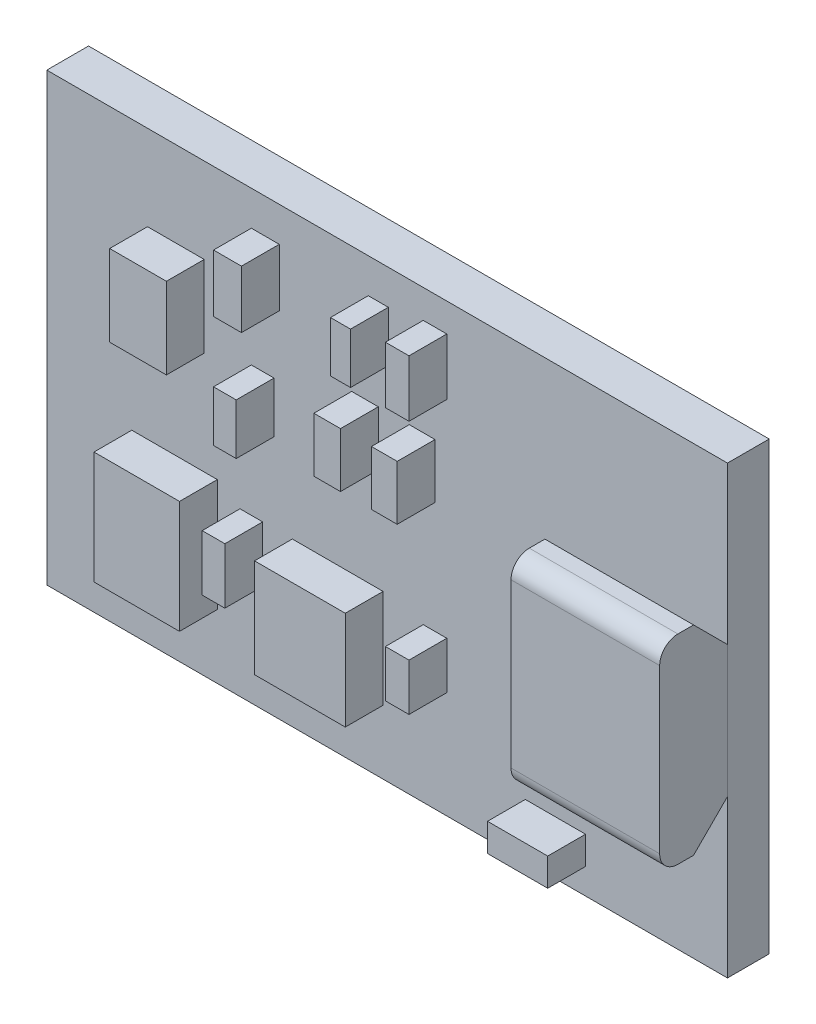
SolidWorks part; units mm, degrees
ref_plane "Спереди" through (0, 0, 0) normal (0, 0, 1) x (1, 0, 0)
ref_plane "Сверху" through (0, 0, 0) normal (0, 1, 0) x (1, 0, 0)
ref_plane "Справа" through (0, 0, 0) normal (1, 0, 0) x (0, 0, -1)
sketch "Эскиз1" plane through (0, 0, 0) normal (0, 0, 1) x (1, 0, 0)
  line L1 (-363.8203, 78.5154) -> (-337.7203, 78.5154)
  line L2 (-363.8203, 78.5154) -> (-363.8203, 61.4154)
  line L3 (-363.8203, 61.4154) -> (-337.7203, 61.4154)
  line L4 (-337.7203, 78.5154) -> (-337.7203, 61.4154)
  dimension "D1" = 17.1
  dimension "D2" = 26.1
extrude "Бобышка-Вытянуть1" add sketch "Эскиз1" along normal blind 1.6
sketch "Эскиз2" plane through (0, 0, 0) normal (0, 0, -1) x (-1, 0, 0)
  line L0 (337.7203, 61.4154) -> (337.7203, 78.5154) construction
  line L1 (350.9253, 67.6511) -> (354.4049, 67.6511)
  line L2 (350.9253, 67.6511) -> (350.9253, 63.8703)
  line L3 (350.9253, 63.8703) -> (354.4049, 63.8703)
  line L4 (354.4049, 67.6511) -> (354.4049, 63.8703)
  line L5 (357.2823, 68.1864) -> (360.5612, 68.1864)
  line L6 (357.2823, 68.1864) -> (357.2823, 63.8703)
  line L7 (357.2823, 63.8703) -> (360.5612, 63.8703)
  line L8 (360.5612, 68.1864) -> (360.5612, 63.8703)
  line L9 (357.7842, 75.2461) -> (359.959, 75.2461)
  line L10 (357.7842, 75.2461) -> (357.7842, 72.1345)
  line L11 (357.7842, 72.1345) -> (359.959, 72.1345)
  line L12 (359.959, 75.2461) -> (359.959, 72.1345)
  line L13 (348.4828, 67.3165) -> (349.3862, 67.3165)
  line L14 (348.4828, 67.3165) -> (348.4828, 65.5098)
  line L15 (348.4828, 65.5098) -> (349.3862, 65.5098)
  line L16 (349.3862, 67.3165) -> (349.3862, 65.5098)
  line L17 (343.163, 63.4688) -> (345.4716, 63.4688)
  line L18 (343.163, 63.4688) -> (343.163, 62.3982)
  line L19 (343.163, 62.3982) -> (345.4716, 62.3982)
  line L20 (345.4716, 63.4688) -> (345.4716, 62.3982)
  line L21 (348.4828, 77.4209) -> (349.3862, 77.4209)
  line L22 (348.4828, 77.4209) -> (348.4828, 75.2461)
  line L23 (348.4828, 75.2461) -> (349.3862, 75.2461)
  line L24 (349.3862, 77.4209) -> (349.3862, 75.2461)
  line L25 (350.7245, 77.1867) -> (351.4941, 77.1867)
  line L26 (350.7245, 77.1867) -> (350.7245, 75.2461)
  line L27 (350.7245, 75.2461) -> (351.4941, 75.2461)
  line L28 (351.4941, 77.1867) -> (351.4941, 75.2461)
  line L29 (348.9345, 73.6903) -> (349.9215, 73.6903)
  line L30 (348.9345, 73.6903) -> (348.9345, 71.5992)
  line L31 (348.9345, 71.5992) -> (349.9215, 71.5992)
  line L32 (349.9215, 73.6903) -> (349.9215, 71.5992)
  line L33 (351.1093, 73.6903) -> (352.1298, 73.6903)
  line L34 (351.1093, 73.6903) -> (351.1093, 71.5992)
  line L35 (351.1093, 71.5992) -> (352.1298, 71.5992)
  line L36 (352.1298, 73.6903) -> (352.1298, 71.5992)
  line L37 (354.9068, 77.1867) -> (355.9775, 77.1867)
  line L38 (354.9068, 77.1867) -> (354.9068, 74.9784)
  line L39 (354.9068, 74.9784) -> (355.9775, 74.9784)
  line L40 (355.9775, 77.1867) -> (355.9775, 74.9784)
  line L41 (355.1076, 72.6447) -> (355.9775, 72.6447)
  line L42 (355.1076, 72.6447) -> (355.1076, 70.6958)
  line L43 (355.1076, 70.6958) -> (355.9775, 70.6958)
  line L44 (355.9775, 72.6447) -> (355.9775, 70.6958)
  line L45 (355.5425, 67.6511) -> (356.4124, 67.6511)
  line L46 (355.5425, 67.6511) -> (355.5425, 65.5098)
  line L47 (355.5425, 65.5098) -> (356.4124, 65.5098)
  line L48 (356.4124, 67.6511) -> (356.4124, 65.5098)
  line L49 (337.7203, 73.7904) -> (343.4203, 73.7904)
  line L50 (337.7203, 73.7904) -> (337.7203, 66.1404)
  line L51 (337.7203, 66.1404) -> (343.4203, 66.1404)
  line L52 (343.4203, 73.7904) -> (343.4203, 66.1404)
  point P52 (337.7203, 69.9654)
  point P55 (337.7203, 69.9654)
  line M7 (337.7203, 78.5154) -> (337.7203, 61.4154)
  dimension "D1" = 7.65
  dimension "D2" = 5.7
extrude "Бобышка-Вытянуть2" add sketch "Эскиз2" against normal blind 2.6 from surface separate body contours L52 L49 L51 M7 region at (-340.5703, 69.9654, 0) starting at face at (-350.7703, 69.9654, 1.6)
extrude "Бобышка-Вытянуть3" add sketch "Эскиз2<3>" against normal blind 3.05 contours L12 L9 L10 L11 | L40 L37 L38 L39 | L28 L25 L26 L27 | L24 L21 L22 L23 | L32 L29 L30 L31 | L44 L41 L42 L43 | L8 L5 L6 L7 | L48 L45 L46 L47 | L4 L1 L2 L3 | L16 L13 L14 L15 | L20 L17 L18 L19 | L36 L35 L34 L33 region at (-352.6651, 65.7607, 0) region at (-358.9218, 66.0284, 0) region at (-358.8716, 73.6903, 0) region at (-348.9345, 66.4131, 0) region at (-344.3173, 62.9335, 0) region at (-348.9345, 76.3335, 0) region at (-351.1093, 76.2164, 0) region at (-349.428, 72.6447, 0) region at (-355.4421, 76.0826, 0) region at (-355.5425, 71.6703, 0) region at (-355.9775, 66.5804, 0)
sketch "Эскиз2<3>" plane through (0, 0, 0) normal (0, 0, -1) x (-1, 0, 0) same geometry as "Эскиз2"
chamfer "Фаска1" distance 1.3 angle 45 2 edges at (-340.5703, 66.1404, 1.6) (-340.5703, 73.7904, 1.6)
fillet "Скругление1" radius 0.7 2 edges at (-340.5703, 73.7904, 4.2) (-340.5703, 66.1404, 4.2)
